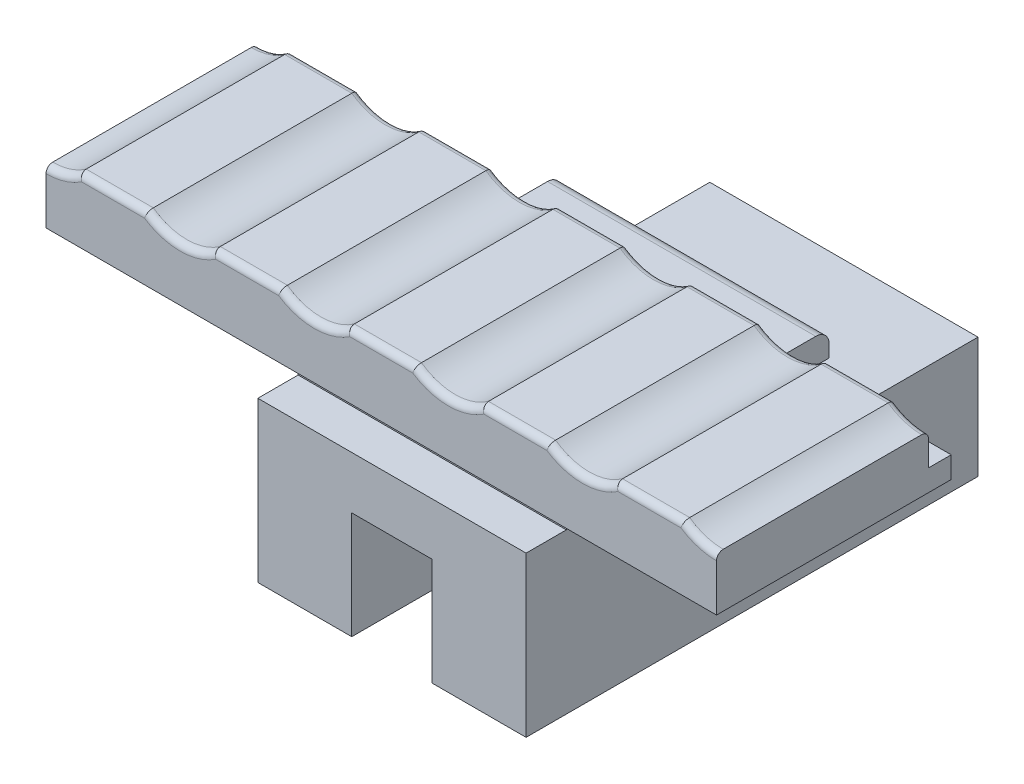
SolidWorks part; units mm, degrees
material "ABS"
ref_plane "Płaszczyzna przednia" through (0, 0, 0) normal (0, 0, 1) x (1, 0, 0)
ref_plane "Płaszczyzna górna" through (0, 0, 0) normal (0, 1, 0) x (1, 0, 0)
ref_plane "Płaszczyzna prawa" through (0, 0, 0) normal (1, 0, 0) x (0, 0, -1)
ref_plane "Plane1" through (0, -4.5937, 0) normal (0, -1, 0) x (1, 0, 0)
sketch "Sketch1" plane through (0, -4.5937, 0) normal (0, -1, 0) x (1, 0, 0)
  line L0 (-15.5276, 6) -> (-15.5276, -0.85)
  line L1 (-15.5276, -0.85) -> (9.4724, -0.85)
  line L2 (9.4724, -0.85) -> (9.4724, 6)
  line L3 (9.4724, 6) -> (-15.5276, 6)
extrude "Boss-Extrude1" add sketch "Sketch1" against normal blind 0.8
sketch "Sketch2" plane through (0, -4.5937, 0) normal (0, -1, 0) x (1, 0, 0)
  line L0 (1.9724, -0.85) -> (-8.0276, -0.85)
  line L1 (-8.0276, -0.85) -> (-8.0276, 6)
  line L2 (-8.0276, 6) -> (1.9724, 6)
  line L3 (1.9724, 6) -> (1.9724, -0.85)
extrude "Boss-Extrude2" add sketch "Sketch2" along normal blind 3.9
sketch "Sketch3" plane through (0, -8.4937, 0) normal (0, -1, 0) x (1, 0, 0)
  line L0 (-4.5276, 0.65) -> (-1.5276, 0.65)
  line L1 (-1.5276, 0.65) -> (-1.5276, 4.5)
  line L2 (-1.5276, 4.5) -> (-4.5276, 4.5)
  line L3 (-4.5276, 4.5) -> (-4.5276, 0.65)
extrude "Cut-Extrude1" cut sketch "Sketch3" against normal blind 4.5
sketch "Sketch4" plane through (0, 0, 6) normal (0, 0, 1) x (1, 0, 0)
  line L0 (0.4724, -4.5937) -> (-6.5276, -4.5937)
  line L1 (-7.5276, -4.5937) -> (-15.5276, -4.5937)
  line L2 (-15.5276, -4.5937) -> (-15.5276, -3.7937)
  line L3 (-15.5276, -3.7937) -> (9.4724, -3.7937)
  line L4 (9.4724, -3.7937) -> (9.4724, -4.5937)
  line L5 (9.4724, -4.5937) -> (1.4724, -4.5937)
  arc A0 (1.4724, -4.5937) -> (0.4724, -4.5937) centre (0.9724, -4.32) cw
  arc A1 (-6.5276, -4.5937) -> (-7.5276, -4.5937) centre (-7.0276, -4.32) cw
extrude "Boss-Extrude3" add sketch "Sketch4" along normal blind 1.5
sketch "Sketch5" plane through (0, 0, -0.85) normal (0, 0, -1) x (-1, 0, 0)
  line L0 (8.0276, -4.9437) -> (8.0276, -7.1437)
  line L1 (8.0276, -7.1437) -> (-1.9724, -7.1437)
  line L2 (-1.9724, -7.1437) -> (-1.9724, -4.9437)
  line L3 (-1.9724, -4.9437) -> (8.0276, -4.9437)
extrude "Boss-Extrude4" add sketch "Sketch5" along normal blind 1
sketch "Sketch6" plane through (0, 0, 7.5) normal (0, 0, 1) x (1, 0, 0)
  line L0 (9.4724, -3.7937) -> (9.4724, -4.5937)
  line L1 (9.4724, -4.5937) -> (-15.5276, -4.5937)
  line L2 (-15.5276, -4.5937) -> (-15.5276, -3.7937)
  line L3 (-15.5276, -3.7937) -> (9.4724, -3.7937)
extrude "Boss-Extrude5" add sketch "Sketch6" along normal blind 0.4
sketch "Sketch7" plane through (0, -3.7937, 0) normal (0, 1, 0) x (-1, 0, 0)
  line L0 (-9.4724, 7.9) -> (15.5276, 7.9)
  line L1 (15.5276, 7.9) -> (15.5276, 0)
  line L2 (15.5276, 0) -> (-9.4724, 0)
  line L3 (-9.4724, 0) -> (-9.4724, 7.9)
extrude "Boss-Extrude6" add sketch "Sketch7" along normal blind 1.6
sketch "Sketch8" plane through (0, 0, -1.85) normal (0, 0, -1) x (-1, 0, 0)
  line L0 (8.0276, -4.9437) -> (8.0276, -5.8937)
  line L1 (8.0276, -5.8937) -> (-1.9724, -5.8937)
  line L2 (-1.9724, -5.8937) -> (-1.9724, -4.9437)
  line L3 (-1.9724, -4.9437) -> (8.0276, -4.9437)
extrude "Boss-Extrude7" add sketch "Sketch8" along normal blind 1.95
sketch "Sketch9" plane through (0, 0, -0.85) normal (0, 0, -1) x (-1, 0, 0)
  line L0 (8.0276, -8.4937) -> (-1.9724, -8.4937)
  line L1 (-1.9724, -8.4937) -> (-1.9724, -7.9937)
  line L2 (-1.9724, -7.9937) -> (8.0276, -7.9937)
  line L3 (8.0276, -7.9937) -> (8.0276, -8.4937)
extrude "Boss-Extrude8" add sketch "Sketch9" along normal blind 8.5
sketch "Sketch10" plane through (0, 0, 6) normal (0, 0, 1) x (1, 0, 0)
  line L0 (-8.0276, -8.4937) -> (-8.0276, -6.5437)
  line L1 (-8.0276, -6.5437) -> (1.9724, -6.5437)
  line L2 (1.9724, -6.5437) -> (1.9724, -8.4937)
  line L3 (1.9724, -8.4937) -> (-8.0276, -8.4937)
extrude "Boss-Extrude9" add sketch "Sketch10" along normal blind 1.5
sketch "Sketch11" plane through (0, -8.4937, 0) normal (0, -1, 0) x (1, 0, 0)
  line L0 (-4.5276, 7.5) -> (-4.5276, -9.35)
  line L1 (-4.5276, -9.35) -> (-8.0276, -9.35)
  line L2 (-8.0276, -9.35) -> (-8.0276, 7.5)
  line L3 (-8.0276, 7.5) -> (-4.5276, 7.5)
extrude "Boss-Extrude10" add sketch "Sketch11" along normal blind 4
sketch "Sketch12" plane through (0, -8.4937, 0) normal (0, -1, 0) x (1, 0, 0)
  line L0 (-1.5276, -9.35) -> (-1.5276, 7.5)
  line L1 (-1.5276, 7.5) -> (1.9724, 7.5)
  line L2 (1.9724, 7.5) -> (1.9724, -9.35)
  line L3 (1.9724, -9.35) -> (-1.5276, -9.35)
extrude "Boss-Extrude11" add sketch "Sketch12" along normal blind 4
ref_plane "Plane2" through (-10.4972, -7.492, 0) normal (0.814, 0.5809, 0) x (-0.5809, 0.814, 0)
sketch "Sketch13" plane through (-10.4972, -7.492, 0) normal (0.814, 0.5809, 0) x (-0.5809, 0.814, 0)
  line L0 (6.5093, 0) -> (8.6593, 0)
  line L1 (8.6593, 0) -> (8.6593, 7.9)
  line L2 (8.6593, 7.9) -> (6.5093, 7.9)
  line L3 (6.5093, 7.9) -> (6.5093, 0)
  line L4 (8.6593, 0) -> (8.6593, 7.9) construction
revolve "Cut-Revolve1" cut sketch "Sketch13" angle 360 about L4 reverse direction yes
ref_plane "Plane3" through (9.4724, 0, 0) normal (1, 0, 0) x (0, 0, -1)
sketch "Sketch14" plane through (9.4724, 0, 0) normal (1, 0, 0) x (0, 0, -1)
  line L0 (0, -2.5937) -> (0, -0.4437)
  line L1 (0, -0.4437) -> (-7.9, -0.4437)
  line L2 (-7.9, -0.4437) -> (-7.9, -2.5937)
  line L3 (-7.9, -2.5937) -> (0, -2.5937)
  line L4 (0, -0.4437) -> (-7.9, -0.4437) construction
revolve "Cut-Revolve2" cut sketch "Sketch14" angle 360 about L4 reverse direction yes
ref_plane "Plane4" through (-7.1846, -5.1277, 0) normal (0.814, 0.5809, 0) x (-0.5809, 0.814, 0)
sketch "Sketch15" plane through (-7.1846, -5.1277, 0) normal (0.814, 0.5809, 0) x (-0.5809, 0.814, 0)
  line L0 (3.6046, 0) -> (5.7546, 0)
  line L1 (5.7546, 0) -> (5.7546, 7.9)
  line L2 (5.7546, 7.9) -> (3.6046, 7.9)
  line L3 (3.6046, 7.9) -> (3.6046, 0)
  line L4 (5.7546, 0) -> (5.7546, 7.9) construction
revolve "Cut-Revolve3" cut sketch "Sketch15" angle 360 about L4 reverse direction yes
sketch3d "3DSketch1"
  point P0 (-2.9961, -6.9022, 1.4399)
  point P1 (97.0039, -6.9022, 1.4399)
ref_axis "Axis1" through (-2.9961, -6.9022, 1.4399) along (1, 0, 0)
pattern_linear "LPattern1" count 4 spacing 5 along (1, 0, 0) of "Cut-Revolve3"
fillet "Fillet1" radius 0.5 1 edges at (-3.0276, -4.9437, -3.8) tangent propagation no
fillet "Fillet2" radius 0.25 11 edges at (-14.8719, -2.4913, 0) (-13.0276, -2.1937, 0) (-10.5276, -2.5937, 0) (-8.0276, -2.1937, 0) (-5.5276, -2.5937, 0) (-3.0276, -2.1937, 0) (-0.5276, -2.5937, 0) (8.8167, -2.4913, 0) (1.9724, -2.1937, 0) (6.9724, -2.1937, 0) (4.4724, -2.5937, 0) tangent propagation no
fillet "Fillet3" radius 0.25 11 edges at (8.8167, -2.4913, 7.9) (6.9724, -2.1937, 7.9) (4.4724, -2.5937, 7.9) (-14.8719, -2.4913, 7.9) (1.9724, -2.1937, 7.9) (-13.0276, -2.1937, 7.9) (-0.5276, -2.5937, 7.9) (-10.5276, -2.5937, 7.9) (-3.0276, -2.1937, 7.9) (-8.0276, -2.1937, 7.9) (-5.5276, -2.5937, 7.9) tangent propagation no
